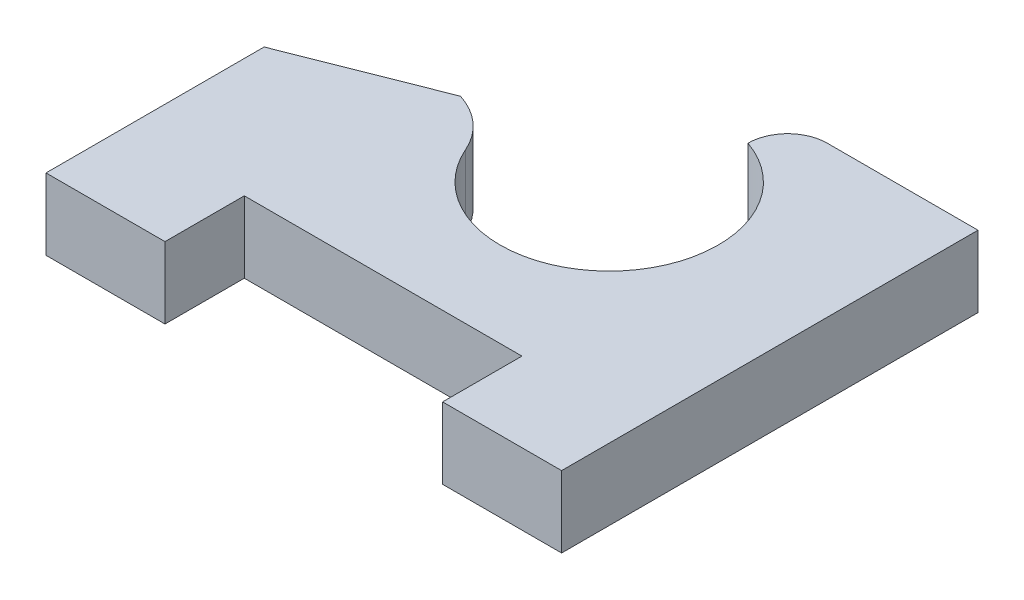
SolidWorks part; units mm, degrees
ref_plane "Front Plane" through (0, 0, 0) normal (0, 0, 1) x (1, 0, 0)
ref_plane "Top Plane" through (0, 0, 0) normal (0, 1, 0) x (1, 0, 0)
ref_plane "Right Plane" through (0, 0, 0) normal (1, 0, 0) x (0, 0, -1)
sketch "Sketch1" plane through (0, 0, 0) normal (0, 1, 0) x (1, 0, 0)
  line L0 (6.5, 2.5) -> (6.5, 0)
  line L1 (3.5, 0) -> (-3.5, 0)
  line L2 (-6.5, 0) -> (-6.5, 2.5)
  line L5 (-6.5, 2.5) -> (-6.5, 3.5)
  line L7 (6.5, 0) -> (6.5, -2)
  line L8 (6.5, -2) -> (3.5, -2)
  line L9 (3.5, 0) -> (3.5, -2)
  line L11 (-6.5, 0) -> (-6.5, -2)
  line L12 (-6.5, -2) -> (-3.5, -2)
  line L13 (-3.5, 0) -> (-3.5, -2)
  line L15 (6.5, 4.9) -> (6.5, 2.5)
  line L17 (-1.95, 4.9) -> (-2.95, 4.9)
  line L18 (-2.95, 4.9) -> (-6.5, 3.5)
  line L19 (1.7, 7.4986) -> (1.7, 8.4986)
  line L20 (1.7, 8.4986) -> (6.5, 8.4986)
  line L21 (6.5, 8.4986) -> (6.5, 4.9)
  arc A2 (-1.95, 4.9) -> (3.3581, 3.8908) centre (0.8, 4.9) ccw
  arc A3 (3.3581, 3.8908) -> (1.7, 7.4986) centre (0.8, 4.9) ccw
  point P0 (0, 0)
  dimension "D1" = 2.4
  dimension "D2" = 5.5
  dimension "D3" = 13
  dimension "D4" = 7.3
  dimension "D5" = 2.5
  dimension "D6" = 1
  dimension "D7" = 1
  dimension "D8" = 2
  dimension "D9" = 3
  dimension "D10" = 3.3
  dimension "D11" = 2.4
  dimension "D12" = 1
  dimension "D13" = 4.8
extrude "Boss-Extrude1" add sketch "Sketch1" along normal blind 1.8
fillet "Fillet1" radius 2 1 edges at (-1.95, 0.9, -4.9)
fillet "Fillet3" radius 1 1 edges at (1.7, 0.9, -8.4986)
ref_plane "Plane1" through (0, 0, 0) normal (0, -1, 0) x (-1, 0, 0)
